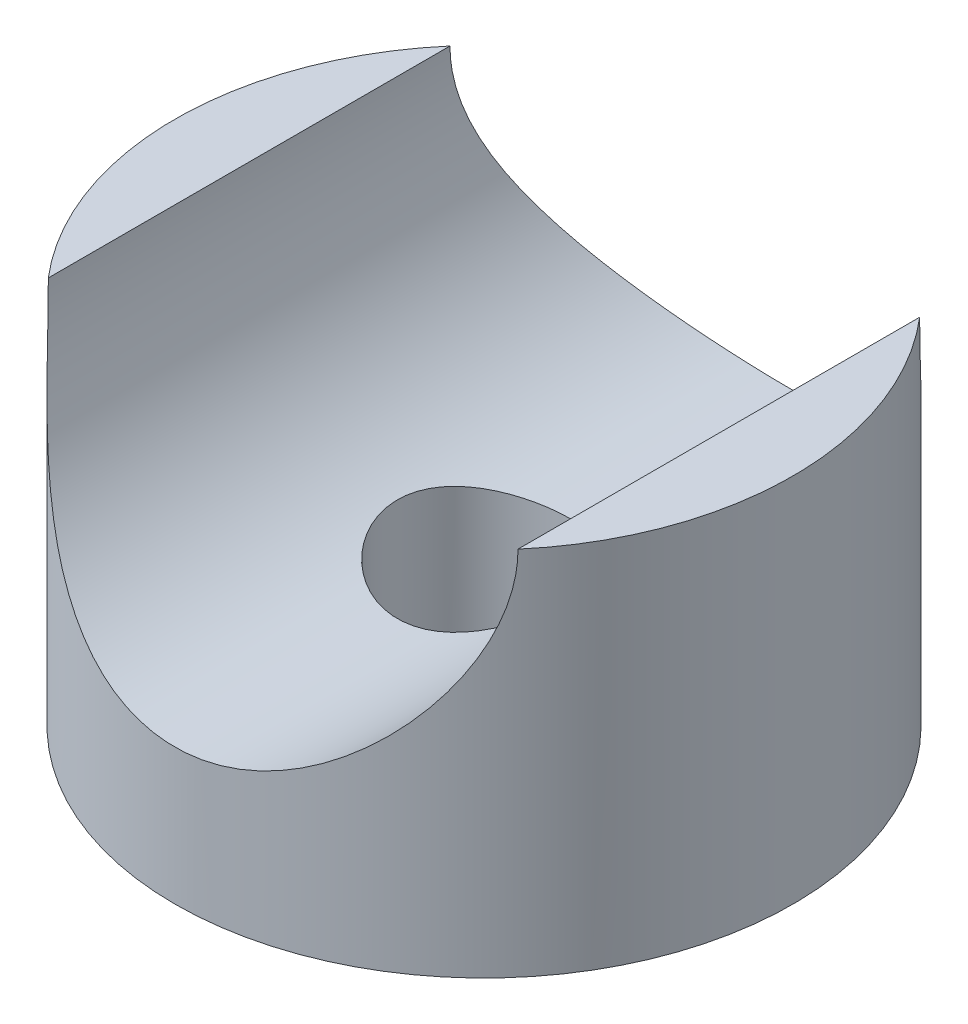
SolidWorks part; units mm, degrees
ref_plane "Front Plane" through (0, 0, 0) normal (0, 0, 1) x (1, 0, 0)
ref_plane "Top Plane" through (0, 0, 0) normal (0, 1, 0) x (1, 0, 0)
ref_plane "Right Plane" through (0, 0, 0) normal (1, 0, 0) x (0, 0, -1)
sketch "Sketch1" plane through (0, 0, 0) normal (0, 1, 0) x (1, 0, 0)
  circle A0 centre (0, 0) radius 12.5
  circle A1 centre (0, 0) radius 3.5
  dimension "D1" = 25
extrude "Boss-Extrude1" add sketch "Sketch1" along normal blind 15
sketch "Sketch2" plane through (0, 0, 0) normal (0, 0, 1) x (1, 0, 0)
  line L0 (12.5, 15) -> (-12.5, 15) construction
  circle A0 centre (0, 15) radius 9.5
  dimension "D1" = 19
extrude "Cut-Extrude1" cut sketch "Sketch2" against normal blind 22 and the other way blind 22
